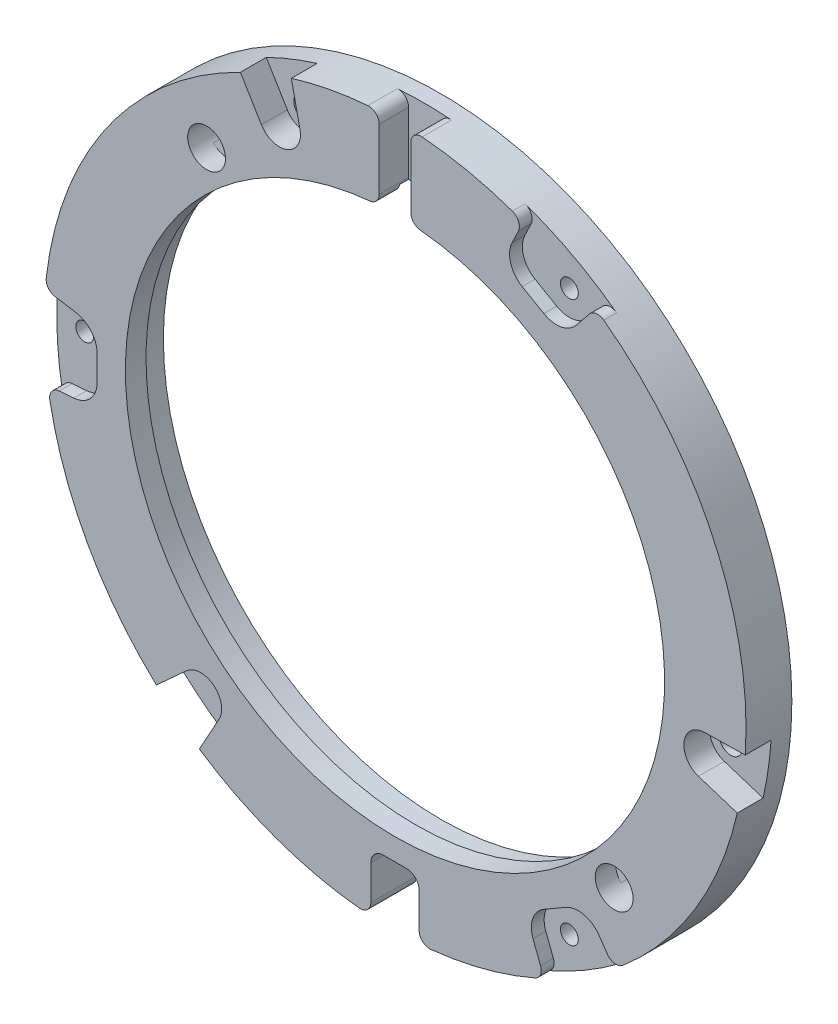
SolidWorks part; units mm, degrees
material "Латунь ЛС59-1Т ГОСТ 15527-2004"
ref_plane "Спереди" through (0, 0, 0) normal (0, 0, 1) x (1, 0, 0)
ref_plane "Сверху" through (0, 0, 0) normal (0, 1, 0) x (1, 0, 0)
ref_plane "Справа" through (0, 0, 0) normal (1, 0, 0) x (0, 0, -1)
sketch "Эскиз1" plane through (0, 0, 0) normal (0, 1, 0) x (1, 0, 0)
  line L0 (0, 0) -> (0, 27.5293) construction
  line L1 (-16.7, 0) -> (-12.825, 0)
  line L2 (-16.7, 0) -> (-16.7, 1.95)
  line L3 (-16.7, 1.95) -> (-13.2, 1.95)
  line L4 (-12.825, 0) -> (-12.825, 0.98)
  line L5 (-13.2, 1.95) -> (-13.2, 0.98)
  line L6 (-13.2, 0.98) -> (-12.825, 0.98)
  dimension "D1" = 25.65
  dimension "D2" = 33.4
  dimension "D3" = 26.4
  dimension "D4" = 0.98
  dimension "D5" = 0.97
revolve "Повернуть1" add sketch "Эскиз1" angle 360 about L0
sketch "Эскиз2" plane through (0, 0, -1.95) normal (0, 0, -1) x (-1, 0, 0)
  line L0 (0, 0) -> (0, -13.86) construction
  line L2 (1.15, -16.6604) -> (1.15, -13.86)
  line L3 (1.15, -13.86) -> (-1.15, -13.86)
  line L4 (-1.15, -16.6604) -> (-1.15, -13.86)
  circle A0 centre (0, 0) radius 16.7 construction
  arc A1 (1.15, -16.6604) -> (-1.15, -16.6604) centre (0, -13.2845) cw
  dimension "D1" = 13.86
  dimension "D2" = 2.3
extrude "Вырез-Вытянуть1" cut sketch "Эскиз2" against normal blind 3
sketch "Эскиз3" plane through (0, 0, 0) normal (0, 0, 1) x (1, 0, 0)
  line L0 (0, 8.3756) -> (0, 0) construction
  line L1 (0, 0) -> (-15.37, 0) construction
  circle A0 centre (-15.37, 0) radius 0.425
  circle A1 centre (0, 0) radius 15.37 construction
  arc A2 (1.15, -16.6604) -> (-1.15, -16.6604) centre (0, 0) ccw construction
  dimension "D1" = 1.33
  dimension "D2" = 0.85
  dimension "D3" = 90
extrude "Вырез-Вытянуть2" cut sketch "Эскиз3" against normal blind 10
cosmetic thread "Условное изображение резьбы1"
sketch "Эскиз4" plane through (0, 0, 0) normal (0, 0, 1) x (1, 0, 0)
  line L0 (-15.1833, 1.1854) -> (-17.3446, 1.5258)
  line L1 (-15.2752, -2.3914) -> (-16.7594, -2.5076)
  line L2 (-16.7594, -2.5076) -> (-17.2931, -0.5259)
  line L3 (-17.2931, -0.5259) -> (-17.3446, 1.5258)
  line L4 (-14.1689, -1.1939) -> (-14.17, 0.0011)
  arc A0 (-15.2752, -2.3914) -> (-14.1689, -1.1939) centre (-15.3689, -1.195) ccw
  circle A1 centre (0, 0) radius 16.7 construction
  arc A2 (-14.8891, 3.8148) -> (-15.292, -1.5469) centre (0, 0) ccw construction
  arc A3 (-15.1833, 1.1854) -> (-14.17, 0.0011) centre (-15.37, 0) cw
  dimension "D3" = 1.9817
extrude "Вырез-Вытянуть3" cut sketch "Эскиз4" against normal blind 0.61
fillet "Скругление1" radius 0.5 2 edges at (-16.5136, -2.4883, -0.305) (-16.64, 1.4148, -0.305)
pattern_circular "Круговой массив1" count 3 over 360 about axis through (0, 0, 0) along (0, 0, 1) of "Вырез-Вытянуть2", "Вырез-Вытянуть3", "Скругление1"
sketch "Эскиз5" plane through (0, 0, 0) normal (0, 0, 1) x (1, 0, 0)
  line L0 (0, 0) -> (0, 9.3924) construction
  line L1 (-0.75, 19.8055) -> (0.75, 19.8055)
  line L2 (-0.75, 19.8055) -> (-0.75, 9.3924)
  line L3 (-0.75, 9.3924) -> (0.75, 9.3924)
  line L4 (0.75, 19.8055) -> (0.75, 9.3924)
  dimension "D1" = 1.5
  dimension "D2" = 9.3924
  dimension "D3" = 10.4131
extrude "Вырез-Вытянуть4" cut sketch "Эскиз5" against normal blind 1.4
sketch "Эскиз6" plane through (0, 0, 0) normal (0, 0, 1) x (1, 0, 0)
  circle A0 centre (-4.036, 11.088) radius 1.425
  circle A1 centre (5.54, -10.419) radius 1.425
  dimension "D1" = 2.85
extrude "Вырез-Вытянуть5" [suppressed] cut sketch "Эскиз6" against normal blind 0.33
fillet "Скругление2" radius 0.6 2 edges at (1.15, -13.86, -0.975) (-1.15, -13.86, -0.975)
sketch "Эскиз22" plane through (0, 0, -1.95) normal (0, 0, -1) x (-1, 0, 0)
  circle A0 centre (-10.4255, -9.7146) radius 0.9
  circle A1 centre (8.9636, 11.0777) radius 0.9
  dimension "D1" = 1.8
  dimension "D2" = 1.8
extrude "Вырез-Вытянуть14" cut sketch "Эскиз22" against normal through all
fillet "Скругление3" radius 0.5 6 edges at (-0.75, 12.8031, -0.49) (0.75, 12.8031, -0.49) (0.75, 16.6832, -0.7) (-0.75, 16.6832, -0.7) (-1.15, -16.6604, -0.975) (1.15, -16.6604, -0.975)
fillet "Скругление4" [suppressed] radius 1
sketch "Эскиз14" plane through (0, 0, 0) normal (0, 0, 1) x (1, 0, 0)
  line L0 (0, 0) -> (0, 22.366) construction
  line L1 (-5.4971, 13.8489) -> (0, 0) construction
  line L2 (0, 0) -> (14.7421, -2.1638) construction
  line L3 (0, 0) -> (-9.2449, -11.6851) construction
  line L4 (0, 0) -> (2.5658, 0) construction
  circle A0 centre (-5.4971, 13.8489) radius 0.55
  circle A1 centre (-9.2449, -11.6851) radius 0.55
  circle A2 centre (14.7421, -2.1638) radius 0.55
  dimension "D1" = 1.1
  dimension "D7" = 14.9
  dimension "D2" = 8.35
  dimension "D3" = 120
  dimension "D4" = 120
  dimension "D5" = 14.9
  dimension "D6" = 14.9
extrude "Вырез-Вытянуть9" cut sketch "Эскиз14" against normal through all
sketch "Эскиз15" plane through (0, 0, 0) normal (0, 0, 1) x (1, 0, 0)
  line L1 (-7.8884, 15.8837) -> (-5.1524, 16.9697)
  line L2 (-5.1524, 16.9697) -> (-4.52, 14.0613)
  line L3 (0, 0) -> (-5.4971, 13.8489) construction
  line L4 (17.6999, -1.1103) -> (17.2724, -4.0228)
  line L5 (-7.8884, 15.8837) -> (-6.354, 13.3333)
  line L6 (17.2724, -4.0228) -> (14.4375, -3.1163)
  line L7 (17.6999, -1.1103) -> (14.724, -1.1639)
  line L8 (0, 0) -> (14.7421, -2.1638) construction
  line L9 (-9.8115, -14.7734) -> (-12.12, -12.9469)
  line L10 (-12.12, -12.9469) -> (-9.9175, -10.9451)
  line L11 (-9.8115, -14.7734) -> (-8.37, -12.1694)
  line L12 (0, 0) -> (-9.2449, -11.6851) construction
  arc A0 (-6.354, 13.3333) -> (-4.52, 14.0613) centre (-5.4971, 13.8489) ccw
  arc A4 (14.724, -1.1639) -> (14.4375, -3.1163) centre (14.7421, -2.1638) ccw
  arc A5 (-8.37, -12.1694) -> (-9.9175, -10.9451) centre (-9.2449, -11.6851) ccw
  point P13 (7.371, -1.0819)
  point P20 (-2.7486, 6.9244)
  point P28 (-4.6225, -5.8426)
  point P29 (0, 0)
  dimension "D1" = 1
  dimension "D3" = 2.5503
  dimension "D4" = 2.9437
  dimension "D2" = 3
extrude "Вырез-Вытянуть10" cut sketch "Эскиз15" against normal blind 1.23
sketch "Эскиз11" plane through (0, 0, 0) normal (0, 0, 1) x (1, 0, 0)
  line L0 (0, 12.825) -> (0, 16.7) construction
  line L1 (0, 0) -> (13.5654, -11.1258) construction
  line L2 (0, 0) -> (16.7363, -3.6124) construction
  line L11 (0, 0) -> (8.9202, 12.9898) construction
  line L192 (0, 0) -> (19.3823, -1.5322) construction
  circle A0 centre (0, 0) radius 14.7625 construction
  arc A1 (15.3147, -1.2106) -> (8.6965, 12.664) centre (0, 0) ccw construction
  arc A2 (7.0859, 12.271) -> (8.6182, 12.5564) centre (7.685, 13.3108) ccw construction
  circle A3 centre (10.4255, -9.7146) radius 0.9 construction
  arc A4 (13.8437, -2.9881) -> (10.9505, -8.9812) centre (0, 0) cw construction
  arc A5 (11.8784, -9.7422) -> (15.0167, -3.2413) centre (0, 0) ccw construction
  arc A6 (14.1185, -1.1161) -> (8.0172, 11.6748) centre (0, 0) ccw construction
  text T0 "JOKER" font "Calibri" height 1.2
  text T1 "METAL" font "Calibri" height 1.2
  point P1 (0, 14.7625)
  dimension "D1" = 0.6
  dimension "D2" = 0.6
  dimension "D3" = 1.2
sketch "Эскиз12" plane through (0, 0, 0) normal (0, 0, 1) x (1, 0, 0)
  line L0 (-12.825, 0) -> (-16.7, 0) construction
  line L1 (0, 0) -> (-9.6261, 10.4685) construction
  line L2 (0, 0) -> (-15.6784, 1.2634) construction
  line L3 (0, 0) -> (2.9304, 13.856) construction
  line L4 (0, 0) -> (0, 21.4261) construction
  line L5 (-15.1833, 1.1854) -> (-16.1735, 1.3414) construction
  line L6 (0, 0) -> (-9.9175, -10.9451) construction
  line L7 (0, 0) -> (-15.6222, -2.4185) construction
  line L8 (0, 0) -> (0.75, 15.4431) construction
  line L9 (-9.6261, 10.4685) -> (-13.3718, 14.542) construction
  line L10 (0, 0) -> (5.5666, 14.4244) construction
  line L11 (0.75, 13.2662) -> (0.75, 16.1517) construction
  line L12 (0.75, 16.1517) -> (0.75, 13.2662) construction
  line L13 (-9.9175, -10.9451) -> (-12.5743, -13.8771) construction
  line L15 (-15.9693, -2.4457) -> (-15.2752, -2.3914) construction
  circle A3 centre (0, 0) radius 14.7625 construction
  circle A4 centre (-8.9636, 11.0777) radius 0.9 construction
  arc A6 (2.7833, 7.2122) -> (0.375, 7.7215) centre (0, 0) ccw construction
  arc A8 (-9.5862, 10.4251) -> (-14.1167, 1.1375) centre (0, 0) ccw construction
  arc A9 (5.5666, 14.4244) -> (0, 15.4613) centre (0, 0) ccw construction
  arc A10 (-13.9958, -2.1667) -> (-9.5096, -10.4949) centre (0, 0) ccw construction
  arc A11 (-10.3154, -11.3842) -> (-15.1816, -2.3503) centre (0, 0) cw construction
  arc A12 (-1.2031, 12.7684) -> (1.2031, 12.7684) centre (0, 0) ccw construction
  arc A13 (-16.5925, 1.8919) -> (-16.4219, -3.0351) centre (0, 0) ccw construction
  arc A14 (-15.3129, 1.2339) -> (-10.3984, 11.3084) centre (0, 0) cw construction
  text T0 "KONSTANTIN" font "Calibri" height 1.2
  text T1 "CHAYKIN" font "Calibri" height 1.2
  point P6 (-14.7625, 0)
  point P43 (-15.6222, -2.4185)
  line B0 (4.7902, 14.9849) -> (2.9104, 13.7614)
  line B1 (2.5203, 13.8432) -> (3.3001, 13.6783)
  line B2 (3.3001, 13.6783) -> (3.4482, 13.4508)
  line B3 (3.4482, 13.4508) -> (2.2929, 13.6951)
  line B4 (2.2929, 13.6951) -> (2.5203, 13.8432)
  line B5 (2.9104, 13.7614) -> (1.6869, 15.6412)
  line B6 (1.6869, 15.6412) -> (2.9913, 14.1438)
  line B7 (2.9913, 14.1438) -> (4.7902, 14.9849)
  line B8 (1.3189, 13.9011) -> (4.4222, 13.2448) construction
  line B9 (4.7902, 14.9849) -> (4.4222, 13.2448) construction
  line B10 (1.6869, 15.6412) -> (4.4222, 13.2448) construction
  line B11 (1.6869, 15.6412) -> (4.7902, 14.9849) construction
  line B12 (1.6869, 15.6412) -> (1.3189, 13.9011) construction
  dimension "D2" = 1.2
  dimension "D3" = 0.6
  dimension "D4" = 1.2
sketch_block_instance "Блок3-1"
sketch_block "Блок3" parameters "D1"=4.6, "D3"=14.4396, "D4"=13.6125, "D2"=14.1625, "D5"=14.381
sketch "Эскиз13" plane through (0, 0, 0) normal (0, 0, 1) x (1, 0, 0)
  line L0 (0, 0) -> (-9.6432, 10.7476) construction
  line L1 (-9.6432, 10.7476) -> (-14.2955, 2.0346) construction
  line L2 (-14.2955, 2.0346) -> (0, 0) construction
  line L3 (0, 0) -> (3.5861, 13.9872) construction
  line L4 (-6.3037, -12.9909) -> (0, 0) construction
  line L5 (0, 0) -> (-13.1793, -5.8997) construction
  line L6 (0, 0) -> (0, 21.7235) construction
  arc A0 (-9.6432, 10.7476) -> (-14.2955, 2.0346) centre (0, 0) ccw construction
  arc A1 (-13.1793, -5.8997) -> (-6.3037, -12.9909) centre (0, 0) ccw construction
  text T0 "METAL" font "Calibri" height 1.4
  text T1 "DRACULA" font "Calibri" height 1.4
  dimension "D2" = 14.4396
  dimension "D1" = 14.4396
  dimension "D3" = 40
  dimension "D4" = 40
  dimension "D5" = 14.38
sketch_block_instance "Блок1-2"
sketch_block "Блок1" parameters "D2"=14.4396, "D1"=14.9694, "D3"=14.2654, "D4"=14.2686, "D5"=21.7235
sketch "Эскиз16" plane through (0, 0, -1.95) normal (0, 0, -1) x (-1, 0, 0)
  arc A2 (1.7009, -16.6132) -> (-1.7009, -16.6132) centre (0, 0) ccw
  circle A3 centre (0, 0) radius 16.7
  dimension "D1" = 0
sketch "Эскиз17" plane through (0, 0, -1.95) normal (0, 0, -1) x (-1, 0, 0)
  arc A2 (-1.2031, 12.7684) -> (1.2031, 12.7684) centre (0, 0) ccw
  circle A3 centre (0, 0) radius 12.825
  dimension "D1" = 0
sketch "Эскиз18" plane through (0, 0, -1.95) normal (0, 0, -1) x (-1, 0, 0)
  arc A2 (1.9148, -18.7022) -> (-1.9148, -18.7022) centre (0, 0) ccw
  circle A3 centre (0, 0) radius 18.8
  dimension "D1" = 2.1
sketch "Эскиз19" plane through (0, 0, -1.95) normal (0, 0, -1) x (-1, 0, 0)
  arc A2 (-1.0999, 11.6733) -> (1.0999, 11.6733) centre (0, 0) ccw
  circle A3 centre (0, 0) radius 11.725
  dimension "D1" = 1.1
sketch "Эскиз21" plane through (0, 0, -1.95) normal (0, 0, -1) x (-1, 0, 0)
  line L0 (0, 0) -> (0, 22.687) construction
  line L1 (0, 0) -> (20.236, -11.6833) construction
  line L2 (0, 0) -> (-21.7168, -12.5382) construction
  circle A0 centre (0, 0) radius 15.795 construction
  circle A1 centre (0, 17.295) radius 1.5
  circle A2 centre (14.9779, -8.6475) radius 1.5
  circle A3 centre (-14.9779, -8.6475) radius 1.5
  dimension "D1" = 31.59
  dimension "D4" = 3
  dimension "D6" = 14.9779
  dimension "D7" = 8.6475
  dimension "D2" = 120
  dimension "D3" = 120
  dimension "D5" = 17.295
sketch "Эскиз23" plane through (0, 0, -1.95) normal (0, 0, -1) x (-1, 0, 0)
  line L3 (1.15, -14.46) -> (1.15, -16.1158)
  line L4 (-1.15, -16.1158) -> (-1.15, -14.46)
  line L5 (-0.55, -13.86) -> (0.55, -13.86)
  line L6 (1.15, -14.46) -> (1.15, -16.1158)
  line L7 (-1.15, -16.1158) -> (-1.15, -14.46)
  line L8 (-0.55, -13.86) -> (0.55, -13.86)
  circle A1 centre (0, 0) radius 13.2
  circle A2 centre (0, 0) radius 13.2
  circle A3 centre (15.37, 0) radius 0.425
  circle A4 centre (15.37, 0) radius 0.425
  circle A5 centre (-7.685, -13.3108) radius 0.425
  circle A6 centre (-7.685, -13.3108) radius 0.425
  circle A7 centre (-7.685, 13.3108) radius 0.425
  circle A8 centre (-7.685, 13.3108) radius 0.425
  circle A9 centre (8.9636, 11.0777) radius 0.9
  circle A10 centre (8.9636, 11.0777) radius 0.9
  circle A11 centre (-10.4255, -9.7146) radius 0.9
  circle A12 centre (-10.4255, -9.7146) radius 0.9
  circle A13 centre (-14.7421, -2.1638) radius 0.55
  circle A14 centre (-14.7421, -2.1638) radius 0.55
  circle A15 centre (9.2449, -11.6851) radius 0.55
  circle A16 centre (9.2449, -11.6851) radius 0.55
  circle A17 centre (5.4971, 13.8489) radius 0.55
  circle A18 centre (5.4971, 13.8489) radius 0.55
  arc A23 (1.15, -16.1158) -> (1.7009, -16.6132) centre (1.65, -16.1158) ccw
  arc A24 (1.7009, -16.6132) -> (-1.7009, -16.6132) centre (0, 0) ccw
  arc A25 (-1.7009, -16.6132) -> (-1.15, -16.1158) centre (-1.65, -16.1158) ccw
  arc A26 (-0.55, -13.86) -> (-1.15, -14.46) centre (-0.55, -14.46) ccw
  arc A27 (1.15, -14.46) -> (0.55, -13.86) centre (0.55, -14.46) ccw
  arc A28 (1.15, -16.1158) -> (1.7009, -16.6132) centre (1.65, -16.1158) ccw
  arc A29 (1.7009, -16.6132) -> (-1.7009, -16.6132) centre (0, 0) ccw
  arc A30 (-1.7009, -16.6132) -> (-1.15, -16.1158) centre (-1.65, -16.1158) ccw
  arc A31 (-0.55, -13.86) -> (-1.15, -14.46) centre (-0.55, -14.46) ccw
  arc A32 (1.15, -14.46) -> (0.55, -13.86) centre (0.55, -14.46) ccw
  dimension "D1" = 0
  dimension "D2" = 0
  dimension "D3" = 0
  dimension "D4" = 0
  dimension "D5" = 0
  dimension "D6" = 0
  dimension "D7" = 0
  dimension "D8" = 0
  dimension "D9" = 0
  dimension "D10" = 0
extrude "Бобышка-Вытянуть1" add sketch "Эскиз23" along normal blind 0.23
other "Переместить грань2" [suppressed] offset 0.02 parameters "D1"=0.02
sketch "Эскиз24" plane through (0, 0, -2.18) normal (0, 0, -1) x (-1, 0, 0)
  line L0 (-9.7672, -10.3283) -> (9.6219, 10.4639)
  line L1 (-11.0837, -9.1008) -> (8.3054, 11.6915)
  circle A0 centre (8.9636, 11.0777) radius 0.9 construction
  circle A1 centre (-10.4255, -9.7146) radius 0.9 construction
  arc A2 (9.6219, 10.4639) -> (8.3054, 11.6915) centre (8.9636, 11.0777) ccw
  arc A3 (-11.0837, -9.1008) -> (-9.7672, -10.3283) centre (-10.4255, -9.7146) ccw
extrude "Вырез-Вытянуть15" cut sketch "Эскиз24" against normal up to surface (1.2 mm away) up to face at (0, -0.0571, -0.98)
sketch "Эскиз25" [suppressed] plane through (0, 0, -2.1) normal (0, 0, -1) x (-1, 0, 0)
  line L0 (8.3054, 11.6915) -> (-11.0837, -9.1008)
  line L1 (-9.7672, -10.3283) -> (9.6219, 10.4639)
  arc A0 (9.6219, 10.4639) -> (8.3054, 11.6915) centre (8.9636, 11.0777) ccw
  arc A1 (-11.0837, -9.1008) -> (-9.7672, -10.3283) centre (-10.4255, -9.7146) ccw
  circle A2 centre (8.9636, 11.0777) radius 0.9 construction
  circle A3 centre (-10.4255, -9.7146) radius 0.9 construction
extrude "Вырез-Вытянуть16" [suppressed] cut sketch "Эскиз25" against normal up to surface (1.1 mm away)
other "Переместить грань3" [suppressed] offset 0.03 parameters "D1"=0.03
other "Переместить грань4" [suppressed] offset 0.03 parameters "D1"=0.03
sketch "Эскиз30" plane through (0, 0, 0) normal (0, 0, 1) x (1, 0, 0)
  line L0 (-30, 30) -> (-30, -30)
  line L1 (-30, -30) -> (30, -30)
  line L2 (30, -30) -> (30, 30)
  line L3 (30, 30) -> (-30, 30)
  circle A0 centre (0, -26) radius 3
  circle A1 centre (-26, 0) radius 3
  circle A2 centre (17.165, -17.165) radius 1.5
  circle A3 centre (-17.165, -17.165) radius 1.5
  circle A4 centre (26, 0) radius 3
  circle A5 centre (0, 26) radius 3
  circle A6 centre (17.165, 17.165) radius 1.5
  circle A7 centre (-17.165, 17.165) radius 1.5
  circle A8 centre (-0.15, -15.2411) radius 1.2
  circle A9 centre (-9.2449, -11.6851) radius 0.6
  circle A10 centre (14.7421, -2.1638) radius 0.6
  circle A11 centre (-5.4971, 13.8489) radius 0.6
sketch "Эскиз31" plane through (0, 0, 0) normal (0, 0, 1) x (1, 0, 0)
  line L0 (-30, -30) -> (30, -30) construction
  line L1 (30, 30) -> (-30, 30) construction
  line L2 (30, -30) -> (30, 30) construction
  line L3 (-30, 30) -> (-30, -30) construction
  line L4 (-30, -30) -> (30, -30)
  line L5 (30, 30) -> (-30, 30)
  line L6 (30, -30) -> (30, 30)
  line L7 (-30, 30) -> (-30, -30)
